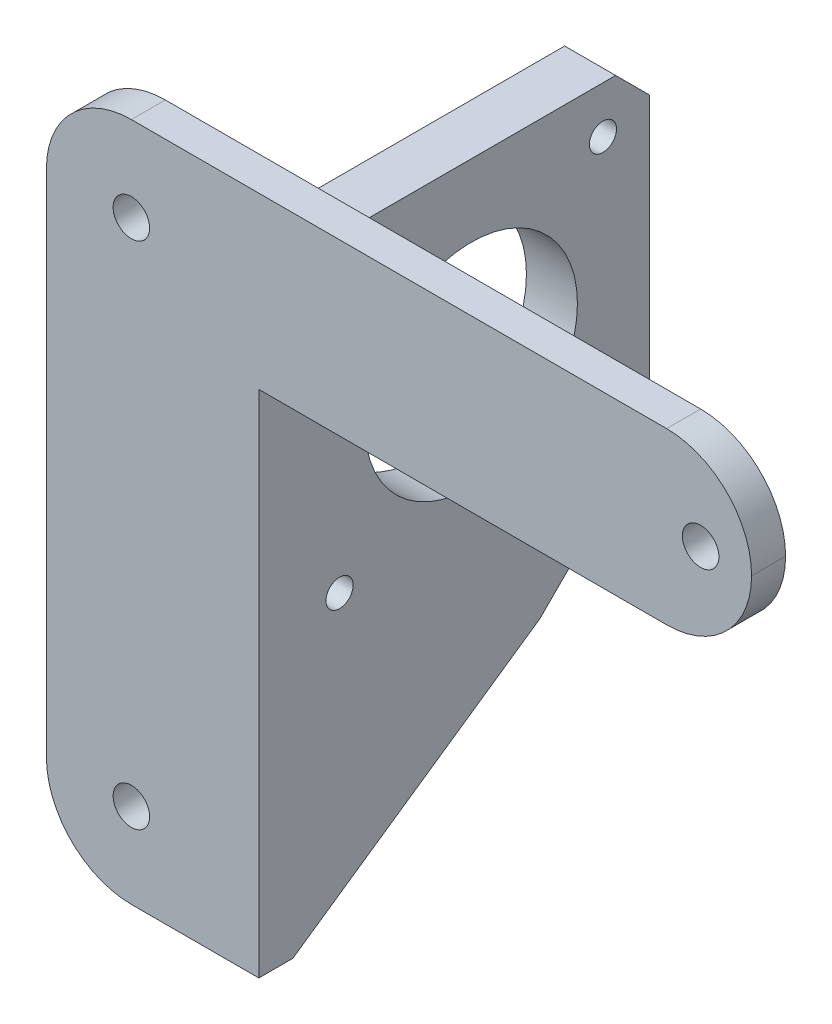
SolidWorks part; units mm, degrees
ref_plane "Plan de face" through (0, 0, 0) normal (0, 0, 1) x (1, 0, 0)
ref_plane "Plan de dessus" through (0, 0, 0) normal (0, 1, 0) x (1, 0, 0)
ref_plane "Plan de droite" through (0, 0, 0) normal (1, 0, 0) x (0, 0, -1)
sketch "Esquisse1" plane through (0, 0, 0) normal (0, 0, 1) x (1, 0, 0)
  line L0 (0, 0) -> (0, -80)
  line L1 (0, -80) -> (25, -80)
  line L2 (25, -80) -> (25, -20)
  line L3 (25, -20) -> (83, -20)
  line L4 (83, -20) -> (83, 0)
  line L5 (83, 0) -> (0, 0)
  dimension "D1" = 80
  dimension "D2" = 25
  dimension "D4" = 58
  dimension "D5" = 20
extrude "Boss.-Extru.1" add sketch "Esquisse1" along normal blind 4
sketch "Esquisse3" plane through (25, 0, 0) normal (1, 0, 0) x (0, 0, -1)
  line L0 (0, -9) -> (42, -9)
  line L1 (0, -20) -> (0, 0) construction
  line L2 (42, -9) -> (42, -51)
  line L3 (42, -51) -> (0, -80)
  line L4 (0, -80) -> (0, -9)
  circle A0 centre (21, -30) radius 12.5
  dimension "D4" = 21
  dimension "D6" = 25
  dimension "D1" = 42
  dimension "D2" = 42
  dimension "D3" = 9
  dimension "D5" = 21
extrude "Boss.-Extru.2" add sketch "Esquisse3" against normal blind 6
hole_wizard "Dégagement M31" positions "Esquisse5" profile "Esquisse4" hole size "M3" standard "Din" end condition through all
sketch "Esquisse5" plane through (25, 0, 0) normal (1, 0, 0) x (0, 0, -1)
  line L3 (42, -9) -> (0, -9) construction
  line L4 (42, -51) -> (42, -9) construction
  point P0 (5.5, -14.5)
  point P2 (36.5, -14.5)
  point P4 (36.5, -45.5)
  point P6 (5.5, -45.5)
  dimension "D1" = 5.5
  dimension "D2" = 5.5
  dimension "D4" = 31
  dimension "D5" = 31
sketch "Esquisse4" plane through (25, -14.5, -5.5) normal (0, 1, 0) x (0, 0, -1)
  line L0 (0, 0) -> (0, 25)
  line L1 (0, 25) -> (1.6, 25)
  line L2 (1.6, 25) -> (1.6, 0)
  line L5 (1.6, 0) -> (0, 0)
  line L11 (0, -6.35) -> (0, 107.95) construction
  dimension "Diamètre du perçage jusqu'au prochain" = 3.2
  dimension "Profondeur du perçage jusqu'au prochain" = 25
hole_wizard "Dégagement M41" positions "Esquisse7" profile "Esquisse6" hole size "M4" standard "Din"
sketch "Esquisse7" plane through (0, 0, 4) normal (0, 0, 1) x (1, 0, 0)
  line L0 (83, 0) -> (0, 0) construction
  line L1 (0, 0) -> (0, -80) construction
  line L2 (0, -80) -> (25, -80) construction
  line L3 (83, -20) -> (83, 0) construction
  line L4 (83, 0) -> (0, 0) construction
  point P0 (10, -10)
  point P2 (10, -70)
  point P11 (77, -10)
  dimension "D1" = 10
  dimension "D2" = 10
  dimension "D3" = 10
  dimension "D4" = 10
  dimension "D5" = 6
  dimension "D6" = 10
sketch "Esquisse6" plane through (10, -10, 4) normal (1, 0, 0) x (0, -1, 0)
  line L0 (0, 0) -> (0, 15)
  line L1 (0, 15) -> (2.15, 15)
  line L2 (2.15, 15) -> (2.15, 0)
  line L5 (2.15, 0) -> (0, 0)
  line L10 (0, 15) -> (-2.15, 15) construction
  line L11 (0, -6.35) -> (0, 107.95) construction
  dimension "Diamètre du perçage" = 4.3
  dimension "Profondeur du perçage" = 15
  dimension "Angle de pointe" = 180
fillet "Congé1" radius 2 2 edges at (22, -9, 0)
chamfer "Chanfrein1" distance 4 angle 45 2 edges at (22, -51, -42) (22, -9, -42)
fillet "Congé2" radius 10 4 edges at (83, -20, 2) (0, -80, 2) (0, 0, 2) (83, 0, 2)
